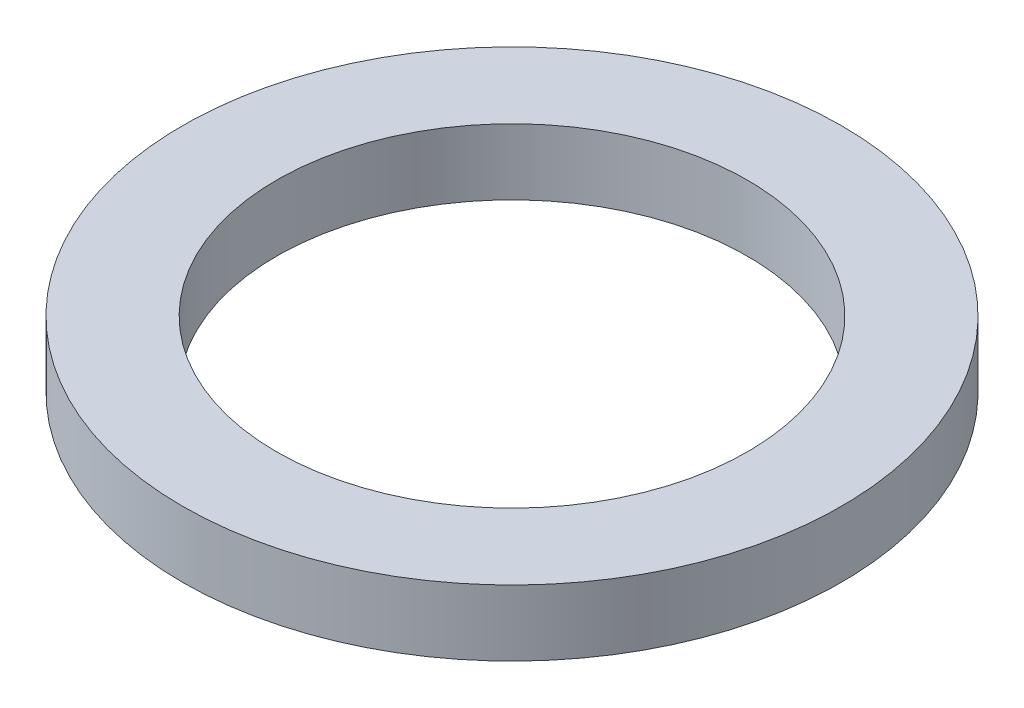
SolidWorks part; units mm, degrees
ref_plane "Front Plane" through (0, 0, 0) normal (0, 0, 1) x (1, 0, 0)
ref_plane "Top Plane" through (0, 0, 0) normal (0, 1, 0) x (1, 0, 0)
ref_plane "Right Plane" through (0, 0, 0) normal (1, 0, 0) x (0, 0, -1)
sketch "Sketch1" plane through (0, 0, 0) normal (0, 1, 0) x (1, 0, 0)
  circle A0 centre (0, 0) radius 70
  dimension "FLANGE_OD" = 140
extrude "Boss-Extrude1" add sketch "Sketch1" along normal blind 14
sketch "Sketch2" plane through (0, 0, 0) normal (0, 1, 0) x (1, 0, 0)
  circle A0 centre (0, 0) radius 50
  dimension "BORE_D" = 100
extrude "Cut-Extrude1" cut sketch "Sketch2" along normal through all
sketch "Sketch3" plane through (0, 14, 0) normal (0, 1, 0) x (1, 0, 0)
  circle A0 centre (0, 0) radius 33.0826 construction
  circle A1 centre (-33.0826, 0) radius 1.7612
  dimension "BOLT_D" = 3.5224
  dimension "BOLT_PCD" = 66.1653
extrude "Cut-Extrude2" cut sketch "Sketch3" against normal blind 13.1291 rebuild error yes
pattern_circular "CirPattern1" count 6 over 360 rebuild error yes
